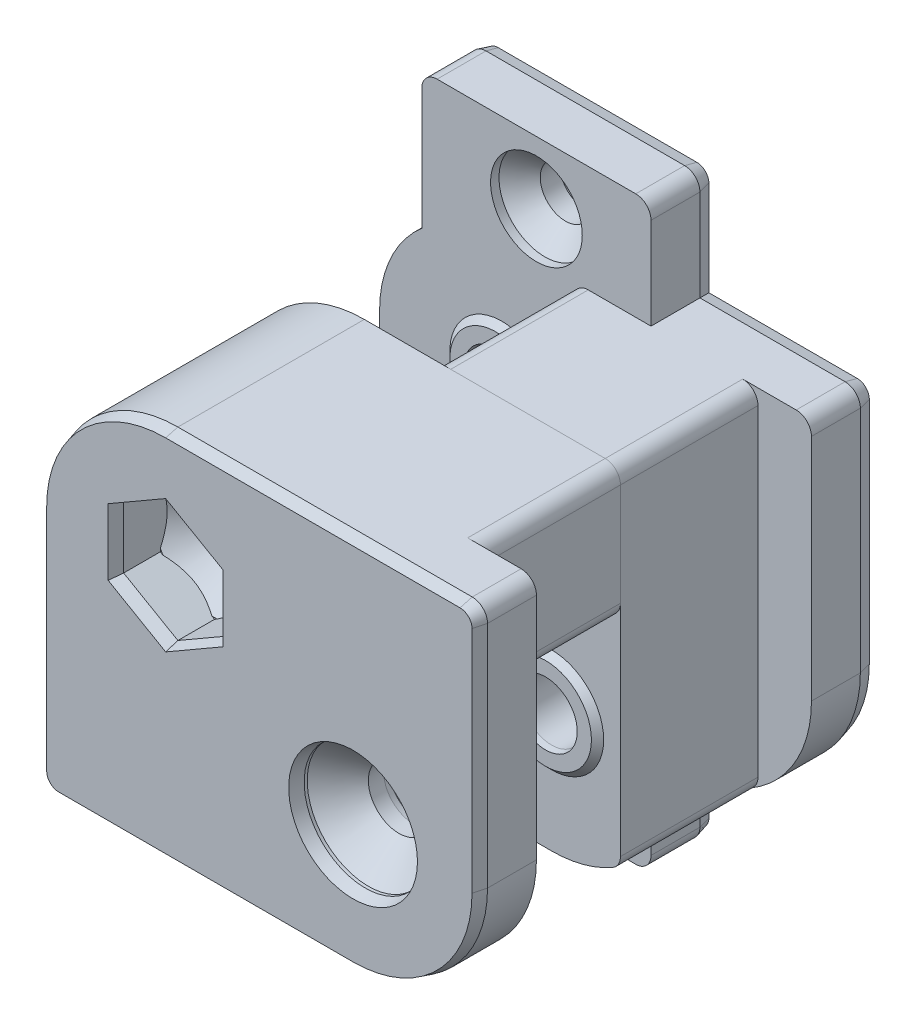
SolidWorks part; units mm, degrees
note: The reader was unsure of these and kept them because the rebuilt part matched: shared geometry of "Sketch", "Sketch", "Sketch", "Sketch", "Sketch", "Sketch", "Sketch".
ref_plane "Спереди" through (0, 0, 0) normal (0, 0, 1) x (1, 0, 0)
ref_plane "Сверху" through (0, 0, 0) normal (0, 1, 0) x (1, 0, 0)
ref_plane "Справа" through (0, 0, 0) normal (1, 0, 0) x (0, 0, -1)
sketch "Sketch1" plane through (0, 0, 0) normal (0, 0, 1) x (1, 0, 0)
  line L11 (0, 0) -> (0, 20.9575) construction
  line L12 (6.1325, -9.5) -> (-34.7302, -9.5) construction
  line L13 (-6.1325, 9.5) -> (-34.7302, 9.5) construction
  line L14 (-0.6325, 4) -> (-0.6325, -25.6347) construction
  line L15 (11.6325, -4) -> (11.6325, 22.5813) construction
  line L16 (-6.1325, 11) -> (-34.7302, 11) construction
  line L17 (6.1325, -11) -> (-34.7302, -11) construction
  line L18 (13.1325, -4) -> (13.1325, 22.5813) construction
  line L19 (0.8675, 4) -> (0.8675, -25.6347) construction
  line L20 (-6.1325, -40.8338) -> (-6.1325, -2.9445) construction
  line L21 (6.1325, -4) -> (-6.1325, 4) construction
  line L22 (0.4481, -40.8338) -> (-12.7131, -40.8338) construction
  circle A8 centre (6.1325, -4) radius 7 construction
  circle A9 centre (-6.1325, 4) radius 7 construction
  circle A10 centre (-6.1325, 4) radius 6.25
  circle A11 centre (6.1325, -4) radius 6.25
  circle A12 centre (6.1325, -4) radius 5.5
  circle A13 centre (-6.1325, 4) radius 5.5
  circle A14 centre (6.1325, -4) radius 2
  circle A15 centre (-6.1325, 4) radius 2
sketch "Sketch2" plane through (0, 0, 0) normal (0, 0, 1) x (1, 0, 0)
  line L4 (0, 0) -> (0, 20.9575) construction
  line L5 (-14.1325, 4) -> (-14.1325, -12)
  line L6 (14.1325, -4) -> (14.1325, 12)
  line L7 (6.1325, -12) -> (-14.1325, -12)
  line L8 (-6.1325, 12) -> (14.1325, 12)
  circle A4 centre (-6.1325, 4) radius 2
  circle A5 centre (6.1325, -4) radius 2
  circle A6 centre (-6.1325, 4) radius 8
  circle A7 centre (6.1325, -4) radius 8
extrude "Extrude1" add sketch "Sketch2" along normal blind 4
extrude "Extrude2" add sketch "Sketch" along normal blind 13 contours L7 A7 A6 L5 | L4 A6 A7 L6 L8 | A6 L4 L8 | A7 A6 A5
sketch "Sketch" plane through (0, 0, 0) normal (0, 0, 1) x (1, 0, 0) same geometry as "Sketch2"
sketch "Sketch3" plane through (0, 0, 13) normal (0, 0, 1) x (1, 0, 0)
  line L0 (6.1325, -12) -> (-14.1325, -12) construction
  line L1 (1.8675, 4) -> (-1.3325, 4)
  line L2 (1.8675, 4) -> (1.8675, -12)
  line L3 (1.8675, -12) -> (-1.3325, -12)
  line L4 (-1.3325, 4) -> (-1.3325, -12)
  line L5 (-0.6325, 4) -> (-0.6325, -25.6347) construction
  line L7 (14.1325, 12) -> (10.6325, 12)
  line L8 (14.1325, 12) -> (14.1325, -16.0848)
  line L9 (14.1325, -16.0848) -> (10.6325, -16.0848)
  line L10 (10.6325, 12) -> (10.6325, -16.0848)
  arc A0 (-14.1325, 4) -> (-6.1325, 12) centre (-6.1325, 4) ccw construction
  arc A1 (-14.1325, 4) -> (-6.1325, 12) centre (-6.1325, 4) ccw construction
  dimension "D1" = 0.7
  dimension "D2" = 3.5
extrude "Extrude3" cut sketch "Sketch3" against normal up to surface (9 mm away) up to face at (-4.1325, 4, 4)
fillet "Fillet1" radius 1 9 edges at (-1.3325, -12, 8.5) (1.8675, -12, 8.5) (14.1325, 12, 2) (-14.1325, -12, 6.5) (-1.3325, -2.4, 8.5) (-14.1325, 4, 8.5) (-6.1325, 12, 8.5) (10.6325, 12, 8.5) (10.6325, -10.6144, 8.5)
extrude "Extrude4" add sketch "Sketch" along normal blind 9 from offset 13 separate body contours L4 A6 A7 L6 L8 | L7 A7 A6 L5 | A6 L4 L8 | A7 L4 A6 A4 | L4 A7 A6 | A4
sketch "Sketch" plane through (0, 0, 0) normal (0, 0, 1) x (1, 0, 0) same geometry as "Sketch2"
sketch "Sketch4" plane through (0, 0, 22) normal (0, 0, 1) x (1, 0, 0)
  line L1 (14.1325, 12) -> (10.6325, 12)
  line L2 (14.1325, 12) -> (14.1325, -6.0345)
  line L3 (14.1325, -6.0345) -> (10.6325, -6.0345)
  line L4 (10.6325, 12) -> (10.6325, -6.0345)
  line L5 (6.1325, -9.5) -> (-34.7302, -9.5) construction
  line L6 (-14.1325, -12) -> (7.4191, -12)
  line L7 (-14.1325, -12) -> (-14.1325, -8.8)
  line L8 (-14.1325, -8.8) -> (7.4191, -8.8)
  line L9 (7.4191, -12) -> (7.4191, -8.8)
  dimension "D1" = 3.5
  dimension "D2" = 0.7
extrude "Extrude5" cut sketch "Sketch4" against normal blind 9
extrude "Extrude6" add sketch "Sketch" along normal blind 4 from vertex at 22
sketch "Sketch" plane through (0, 0, 0) normal (0, 0, 1) x (1, 0, 0) same geometry as "Sketch2"
sketch "Sketch11" plane through (0, 0, 26) normal (0, 0, 1) x (1, 0, 0)
  circle A0 centre (6.1325, -4) radius 4
  dimension "D1" = 8
extrude "Extrude17" cut sketch "Sketch11" against normal blind 1
fillet "Fillet2" radius 1 6 edges at (-14.1325, -12, 24) (-0.2675, -8.8, 17.5) (10.6325, 2.6144, 17.5) (14.1325, 12, 24)
chamfer "Chamfer1" distance 2 angle 45 1 edges at (8.1325, -4, 25)
sketch "Sketch5" plane through (0, 0, 0) normal (0, 0, -1) x (-1, 0, 0)
  line L0 (3.8675, 19) -> (3.8675, -19) construction
  line L1 (11.3675, -19) -> (-3.6325, -19)
  line L2 (11.3675, -19) -> (11.3675, 19)
  line L3 (11.3675, 19) -> (-3.6325, 19)
  line L4 (-3.6325, -19) -> (-3.6325, 19)
  line L5 (11.3675, 0) -> (-3.6325, 0) construction
  circle A0 centre (3.8675, 14.9) radius 1.65
  circle A1 centre (3.8675, -14.9) radius 1.65
  line M1 (6.1325, 12) -> (-13.1325, 12)
  line M5 (-6.1325, -12) -> (13.1325, -12)
  arc M8 (14.1325, 4) -> (6.1325, 12) centre (6.1325, 4) ccw
  dimension "D1" = 3.3
  dimension "D2" = 4.1
  dimension "D3" = 38
  dimension "D4" = 2.5
  dimension "D5" = 15
extrude "Extrude7" add sketch "Sketch5" against normal blind 4 contours L4 L2 L3 A0 M1 M8 | L4 L1 L2 A1 M5
sketch "Sketch6" plane through (0, 0, 4) normal (0, 0, 1) x (1, 0, 0)
  circle A1 centre (-3.8675, -14.9) radius 3
  dimension "D1" = 6
extrude "Extrude8" cut sketch "Sketch6" along normal blind 14 draft 3
sketch "Sketch9" plane through (0, 0, 4) normal (0, 0, 1) x (1, 0, 0)
  circle A0 centre (-3.8675, 14.9) radius 3
  circle A1 centre (-3.8675, -14.9) radius 3
  dimension "D1" = 6
  dimension "D2" = 6
extrude "Extrude15" cut sketch "Sketch9" against normal blind 0.4
sketch "Sketch10" plane through (0, 0, 0) normal (0, 0, -1) x (-1, 0, 0)
  circle A0 centre (6.1325, 4) radius 4
  dimension "D1" = 8
extrude "Extrude16" cut sketch "Sketch10" against normal blind 1
chamfer "Chamfer2" distance 1.5 angle 45 2 edges at (-2.2175, -14.9, 3.6) (-2.2175, 14.9, 3.6)
sketch "Sketch7" plane through (0, 0, 0) normal (0, 0, -1) x (-1, 0, 0)
  line L1 (6.1325, 8.0992) -> (2.5825, 6.0496)
  line L2 (2.5825, 6.0496) -> (2.5825, 1.9504)
  line L3 (2.5825, 1.9504) -> (6.1325, -0.0992)
  line L4 (6.1325, -0.0992) -> (9.6825, 1.9504)
  line L5 (9.6825, 1.9504) -> (9.6825, 6.0496)
  line L6 (9.6825, 6.0496) -> (6.1325, 8.0992)
  line L7 (-6.1325, 0.0992) -> (-9.6825, -1.9504)
  line L8 (-9.6825, -1.9504) -> (-9.6825, -6.0496)
  line L9 (-9.6825, -6.0496) -> (-6.1325, -8.0992)
  line L10 (-6.1325, -8.0992) -> (-2.5825, -6.0496)
  line L11 (-2.5825, -6.0496) -> (-2.5825, -1.9504)
  line L12 (-2.5825, -1.9504) -> (-6.1325, 0.0992)
  circle A0 centre (6.1325, 4) radius 3.55 construction
  circle A1 centre (-6.1325, -4) radius 3.55 construction
  circle M16 centre (-6.1325, -4) radius 2
  dimension "D1" = 7.1
extrude "Extrude9" cut sketch "Sketch7" against normal blind 3.2 contours L11 L12 L7 L8 L9 L10 M16
extrude "Extrude10" cut sketch "Sketch" along normal blind 3.2 from vertex contours L1 L2 L3 L4 L5 L6
sketch "Sketch" plane through (0, 0, 0) normal (0, 0, -1) x (-1, 0, 0) same geometry as "Sketch7"
chamfer "Chamfer3" distance 2 angle 45 1 edges at (-8.1325, 4, 22.8)
chamfer "Chamfer7" distance 2 angle 45 1 edges at (-8.1325, 4, 1)
chamfer "Chamfer4" distance 2 angle 45 1 edges at (4.1325, -4, 3.2)
sketch "Sketch8" plane through (0, 0, 13) normal (0, 0, 1) x (1, 0, 0)
  line L0 (-6.1325, 12) -> (9.6325, 12) construction
  line L3 (10.6325, 11) -> (10.6325, -10.0622) construction
  line L4 (-14.1325, -1.6569) -> (-14.1325, -11) construction
  line L5 (-2.0259, -8.8) -> (-13.1325, -8.8) construction
  circle A0 centre (6.6325, 8) radius 2
  circle A1 centre (-11.1325, -5.8) radius 2
  dimension "D1" = 4
  dimension "D4" = 4
  dimension "D2" = 4
  dimension "D3" = 4
  dimension "D5" = 3
  dimension "D6" = 3
extrude "Extrude11" cut sketch "Sketch8" against normal blind 3.2 draft 3 contours A1
extrude "Extrude12" cut sketch "Sketch" along normal blind 3.2 draft 3 contours A0
sketch "Sketch" plane through (0, 0, 13) normal (0, 0, 1) x (1, 0, 0) same geometry as "Sketch8"
extrude "Extrude13" add sketch "Sketch" along normal blind 3 draft 5 contours A0
sketch "Sketch" plane through (0, 0, 13) normal (0, 0, 1) x (1, 0, 0) same geometry as "Sketch8"
extrude "Extrude14" add sketch "Sketch" against normal blind 3 draft 5 contours A1
sketch "Sketch" plane through (0, 0, 13) normal (0, 0, 1) x (1, 0, 0) same geometry as "Sketch8"
fillet "Fillet3" radius 1 4 edges at (-11.3675, -19, 2) (3.6325, -19, 2) (-11.3675, 19, 2) (3.6325, 19, 2)
chamfer "Chamfer5" distance 0.8 angle 15 28 edges at (-10.1325, 4, 0) (4.3575, -7.0744, 0) (7.9075, -7.0744, 0) (9.6825, -4, 0) (7.9075, -0.9256, 0) (4.3575, -0.9256, 0) (2.5825, -4, 0) (-5.5175, 14.9, 0) (-5.5175, -14.9, 0) (-11.3675, -15, 0) (3.6325, -15, 0) (-11.0746, -18.7071, 0) (3.3396, -18.7071, 0) (-3.8675, -19, 0) (-12.25, -12, 0) (-13.8396, -11.7071, 0) (-14.1325, -3.5, 0) (-13.4085, 7.3257, 0) (-11.3675, 14.0247, 0) (-11.0746, 18.7071, 0) (-3.8675, 19, 0) (3.6325, 15, 0) (3.3396, 18.7071, 0) (4.8825, -12, 0) (11.7894, -9.6569, 0) (14.1325, 3.5, 0) (13.8396, 11.7071, 0) (8.3825, 12, 0)
chamfer "Chamfer6" distance 0.8 angle 15 15 edges at (10.1325, -4, 26) (-7.9075, 0.9256, 26) (-9.6825, 4, 26) (-7.9075, 7.0744, 26) (-4.3575, 7.0744, 26) (-2.5825, 4, 26) (-4.3575, 0.9256, 26) (-14.1325, -3.5, 26) (-13.8396, -11.7071, 26) (-11.7894, 9.6569, 26) (-3.5, -12, 26) (3.5, 12, 26) (11.7894, -9.6569, 26) (13.8396, 11.7071, 26) (14.1325, 3.5, 26)
sketch "Sketch12" plane through (0, 0, 13) normal (0, 0, 1) x (1, 0, 0)
  circle A2 centre (6.1325, -4) radius 3
  circle A3 centre (6.1325, -4) radius 3
  circle M2 centre (6.1325, -4) radius 2
  dimension "D1" = 1
extrude "Extrude18" add sketch "Sketch12" along normal blind 0.4 draft 10 contours A3 M2
sketch "Sketch13" plane through (0, 0, 4) normal (0, 0, 1) x (1, 0, 0)
  circle A2 centre (-6.1325, 4) radius 3
  circle A3 centre (-6.1325, 4) radius 3
  circle M28 centre (-6.1325, 4) radius 2
  dimension "D1" = 1
extrude "Extrude19" add sketch "Sketch13" along normal blind 0.4 draft 10 contours A3 M28
sketch "Sketch14" plane through (0, 0, 13) normal (0, 0, -1) x (-1, 0, 0)
  circle A2 centre (6.1325, 4) radius 3
  circle A3 centre (6.1325, 4) radius 3
  circle M13 centre (6.1325, 4) radius 2
  dimension "D1" = 1
extrude "Extrude20" add sketch "Sketch14" along normal blind 0.4 draft 10 contours A3 M13
sketch "Sketch15" plane through (0, 0, 22) normal (0, 0, -1) x (-1, 0, 0)
  circle A2 centre (-6.1325, -4) radius 3
  circle A3 centre (-6.1325, -4) radius 3
  circle M16 centre (-6.1325, -4) radius 2
  dimension "D1" = 1
extrude "Extrude21" add sketch "Sketch15" along normal blind 0.4 draft 10 contours A3 M16
chamfer "Chamfer8" distance 0.4 angle 45 3 edges at (-3.1325, 4, 13) (3.203, -4, 21.6) (9.1325, -4, 22)
chamfer "Chamfer9" distance 0.4 angle 45 3 edges at (9.1325, -4, 13) (-3.203, 4, 4.4) (-3.1325, 4, 4)
